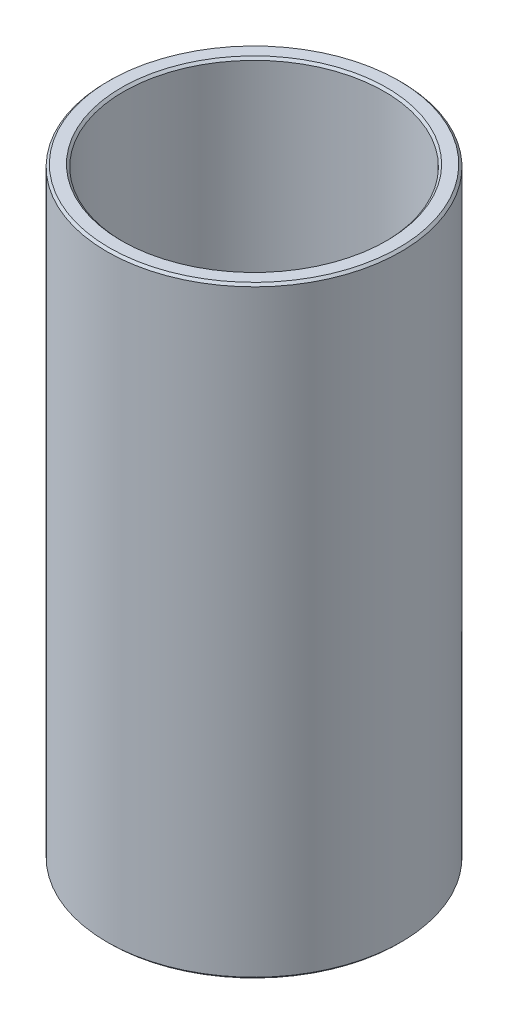
SolidWorks part; units mm, degrees
ref_plane "Front Plane" through (0, 0, 0) normal (0, 0, 1) x (1, 0, 0)
ref_plane "Top Plane" through (0, 0, 0) normal (0, 1, 0) x (1, 0, 0)
ref_plane "Right Plane" through (0, 0, 0) normal (1, 0, 0) x (0, 0, -1)
sketch "Sketch1" plane through (0, 0, 0) normal (0, 1, 0) x (1, 0, 0)
  circle A0 centre (0, 0) radius 37.5
  dimension "SLEEVE_OD" = 75
extrude "Boss-Extrude1" add sketch "Sketch1" along normal blind 153.6427
sketch "Sketch2" plane through (0, 0, 0) normal (0, 1, 0) x (1, 0, 0)
  circle A0 centre (0, 0) radius 33.2537
  dimension "BORE_D" = 66.5075
extrude "Cut-Extrude1" cut sketch "Sketch2" along normal through all
chamfer "Chamfer1" distance 0.58 angle 45 4 edges at (0, 153.6427, 33.2537) (0, 0, 33.2537) (0, 0, 37.5) (0, 153.6427, 37.5)
